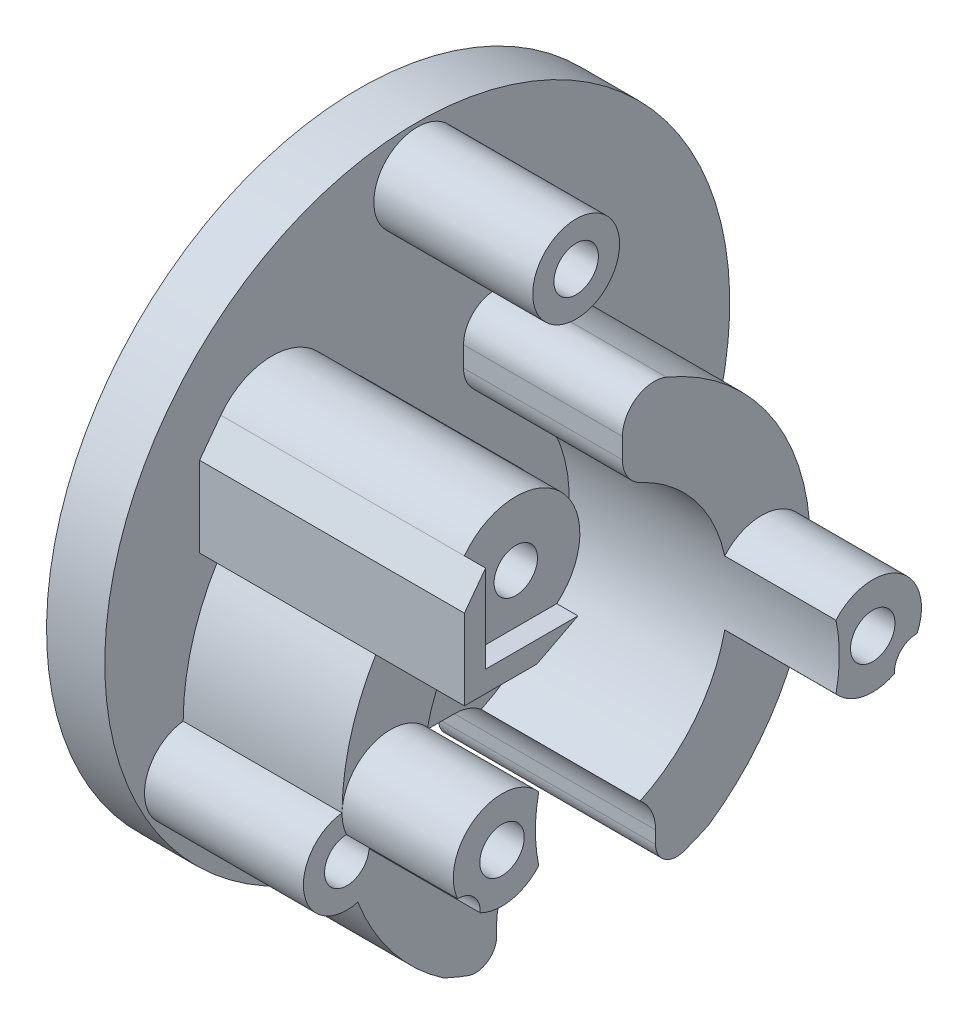
SolidWorks part; units mm, degrees
note: The reader was unsure of these and kept them because the rebuilt part matched: shared geometry of "Sketch1<3>", "Sketch1<4>", "Sketch1<5>", "Sketch3<2>", "Sketch7<4>".
material "ABS"
ref_plane "Front Plane" through (0, 0, 0) normal (0, 0, 1) x (1, 0, 0)
ref_plane "Top Plane" through (0, 0, 0) normal (0, 1, 0) x (1, 0, 0)
ref_plane "Right Plane" through (0, 0, 0) normal (1, 0, 0) x (0, 0, -1)
sketch "Sketch1" plane through (0, 0, 0) normal (1, 0, 0) x (0, 0, -1)
  line L0 (-17.5, -8.5) -> (17.5, -8.5) construction
  line L1 (-8.1298, -20.3249) -> (-12.5205, -26.7112) construction
  line L2 (8.1298, -20.3249) -> (12.5205, -26.7112) construction
  circle A0 centre (0, 0) radius 29.5
  circle A1 centre (-17.5, -8.5) radius 2.1
  circle A2 centre (17.5, -8.5) radius 2.1
  arc A3 (-14.0289, -5.4814) -> (-14.0289, -11.5186) centre (-17.5, -8.5) ccw
  arc A4 (14.0289, -11.5186) -> (14.0289, -5.4814) centre (17.5, -8.5) ccw
  arc A5 (-14.0289, -11.5186) -> (14.0289, -11.5186) centre (0, -8.5) ccw
  arc A6 (-22.1, -8.5) -> (-12.5205, -26.7112) centre (0, -8.5) ccw
  arc A7 (12.5205, -26.7112) -> (22.1, -8.5) centre (0, -8.5) ccw
  arc A8 (12.5205, -26.7112) -> (-12.5205, -26.7112) centre (0, -8.5) ccw
  circle A9 centre (0, -8.5) radius 14.35
  arc A10 (-12.5205, -26.7112) -> (-8.1298, -20.3249) centre (-10.3252, -23.518) ccw
  arc A11 (8.1298, -20.3249) -> (12.5205, -26.7112) centre (10.3252, -23.518) ccw
  circle A12 centre (17.5, -8.5) radius 4.6 construction
  circle A13 centre (-17.5, -8.5) radius 4.6 construction
  dimension "D1" = 4.2
  dimension "D2" = 4.2
  dimension "D4" = 59
  dimension "D8" = 28.7
  dimension "D3" = 35
  dimension "D5" = 17.5
  dimension "D6" = 8.5
  dimension "D7" = 2.5
extrude "Boss-Extrude1" add sketch "Sketch1" along normal blind 3 contours A0 A7 A4 A5 A3 A6 | L0 A3 A5 A4 | A9
extrude "Boss-Extrude2" add sketch "Sketch1<3>" along normal blind 28.5 contours A3 A1 | A4 A2
sketch "Sketch1<3>" plane through (0, 0, 0) normal (1, 0, 0) x (0, 0, -1) same geometry as "Sketch1"
extrude "Boss-Extrude3" add sketch "Sketch1<4>" along normal blind 18 contours A9 A5 | A9 A4 A8 A3 | A8 A7 A0 A6
sketch "Sketch1<4>" plane through (0, 0, 0) normal (1, 0, 0) x (0, 0, -1) same geometry as "Sketch1"
extrude "Boss-Extrude4" add sketch "Sketch1<5>" along normal blind 18 contours A9 A4 A8 A3
sketch "Sketch1<5>" plane through (0, 0, 0) normal (1, 0, 0) x (0, 0, -1) same geometry as "Sketch1"
sketch "Sketch3" plane through (0, 0, 0) normal (-1, 0, 0) x (0, 0, 1)
  line L0 (0, 0) -> (0, 29.5) construction
  circle A0 centre (0, 0) radius 29.5 construction
  circle A1 centre (0, 25) radius 2.1
  circle A2 centre (0, 25) radius 4.1
  circle A3 centre (21.6506, -12.5) radius 4.1
  circle A4 centre (21.6506, -12.5) radius 2.1
  circle A5 centre (-21.6506, -12.5) radius 4.1
  circle A6 centre (-21.6506, -12.5) radius 2.1
  dimension "D1" = 4.2
  dimension "D2" = 25
  dimension "D3" = 2
  dimension "D4" = 3
extrude "Boss-Extrude5" add sketch "Sketch3" against normal up to surface (18 mm away) up to face at (18, -8.5, -19.6)
extrude "Cut-Extrude1" cut sketch "Sketch3<2>" against normal through all contours A6 | L0 A1 | A1 L0 | A4
sketch "Sketch3<2>" plane through (0, 0, 0) normal (-1, 0, 0) x (0, 0, 1) same geometry as "Sketch3"
sketch "Sketch4" plane through (18, 0, 0) normal (1, 0, 0) x (0, 0, -1)
  line L0 (0, -22.75) -> (0, -29.5) construction
  line L1 (-7.5, -22.75) -> (-7.5, -29.5)
  line L2 (7.5, -22.75) -> (7.5, -29.5)
  line L7 (-7.5, -22.75) -> (-7.5, -20.6166)
  line L8 (-7.5, -20.6166) -> (7.5, -20.6166)
  line L9 (7.5, -22.75) -> (7.5, -20.6166)
  line L11 (-7.5, -29.5) -> (-7.5, -30.4306)
  line L12 (-7.5, -30.4306) -> (7.5, -30.4306)
  line L13 (7.5, -29.5) -> (7.5, -30.4306)
  dimension "D1" = 7.5
  dimension "D2" = 7.5
extrude "Cut-Extrude4" cut sketch "Sketch4" against normal through all
fillet "Fillet1" radius 4 2 edges at (1.5, -20.6166, -7.5) (1.5, -20.6166, 7.5)
fillet "Fillet2" radius 2 2 edges at (9, -28.5307, 7.5) (9, -28.5307, -7.5)
sketch "Sketch5" plane through (0, 0, 0) normal (-1, 0, 0) x (0, 0, 1)
  line L3 (7.5, -24.6166) -> (7.5, -25.807)
  line L4 (-7.5, -25.807) -> (-7.5, -24.6166)
  line L5 (-3.5, -20.6166) -> (3.5, -20.6166)
  line L6 (7.5, -24.6166) -> (7.5, -25.807)
  line L7 (-7.5, -25.807) -> (-7.5, -24.6166)
  line L8 (-3.5, -20.6166) -> (3.5, -20.6166)
  circle A0 centre (21.6506, -12.5) radius 2.1 construction
  circle A1 centre (0, 25) radius 2.1 construction
  circle A2 centre (-21.6506, -12.5) radius 2.1 construction
  circle A3 centre (21.6506, -12.5) radius 2.1
  circle A4 centre (0, 25) radius 2.1
  arc A5 (7.5, -25.807) -> (10.1909, -27.6838) centre (9.5, -25.807) ccw
  arc A6 (10.1909, -27.6838) -> (-10.1909, -27.6838) centre (0, 0) ccw
  arc A7 (-10.1909, -27.6838) -> (-7.5, -25.807) centre (-9.5, -25.807) ccw
  arc A8 (-3.5, -20.6166) -> (-7.5, -24.6166) centre (-3.5, -24.6166) ccw
  arc A9 (7.5, -24.6166) -> (3.5, -20.6166) centre (3.5, -24.6166) ccw
  arc A10 (7.5, -25.807) -> (10.1909, -27.6838) centre (9.5, -25.807) ccw
  arc A11 (10.1909, -27.6838) -> (-10.1909, -27.6838) centre (0, 0) ccw
  arc A12 (-10.1909, -27.6838) -> (-7.5, -25.807) centre (-9.5, -25.807) ccw
  arc A13 (-3.5, -20.6166) -> (-7.5, -24.6166) centre (-3.5, -24.6166) ccw
  arc A14 (7.5, -24.6166) -> (3.5, -20.6166) centre (3.5, -24.6166) ccw
  circle A15 centre (-21.6506, -12.5) radius 2.1
  dimension "D1" = 0
extrude "Boss-Extrude6" add sketch "Sketch5" along normal blind 2.5
sketch "Sketch6" plane through (3, 0, 0) normal (1, 0, 0) x (0, 0, -1)
  line L0 (-17.2374, 23.9399) -> (-1.8128, 23.9399)
  line L1 (-17.2374, 22.9399) -> (-2.1475, 22.9399)
  line L2 (-18.5475, 22.094) -> (-18.5475, 6.5399)
  line L3 (-18.5475, 6.5399) -> (-2.1475, 6.5399)
  line L4 (-2.1475, 22.9399) -> (-2.1475, 6.5399)
  line L5 (-1.1475, 23.2412) -> (-1.1475, 5.804)
  line L6 (-19.5475, 5.5399) -> (-2.9669, 5.5399)
  line L7 (-19.5475, 22.094) -> (-19.5475, 5.5399)
  line L8 (-19.5475, 23.9399) -> (-1.1475, 23.9399) construction
  line L9 (-19.5475, 23.9399) -> (-19.5475, 5.5399) construction
  line L10 (-1.1475, 23.9399) -> (-1.1475, 5.5399) construction
  line L11 (-19.5475, 5.5399) -> (-1.1475, 5.5399) construction
  line L12 (-19.5475, 22.094) -> (-18.5475, 22.094)
  line L13 (-17.2374, 23.9399) -> (-17.2374, 22.9399)
  line L14 (-18.5475, 22.9399) -> (-2.1475, 22.9399) construction
  line L15 (-18.5475, 22.9399) -> (-18.5475, 6.5399) construction
  arc A0 (14.0289, -5.4814) -> (-14.0289, -5.4814) centre (0, -8.5) ccw construction
  arc A1 (-1.1475, 5.804) -> (-2.9669, 5.5399) centre (0, -8.5) ccw
  circle A2 centre (0, 25) radius 2.1 construction
  arc A3 (-1.8128, 23.9399) -> (-1.1475, 23.2412) centre (0, 25) ccw
  dimension "D4" = 1
sketch "Sketch7" plane through (3, 0, 0) normal (1, 0, 0) x (0, 0, -1)
  line L0 (-13.7, 11.2) -> (-18.55, 11.2) construction
  line L1 (-13.7, 11.2) -> (-13.7, 6.55) construction
  line L2 (-18.55, 11.2) -> (-18.55, 6.55)
  line L3 (-18.55, 6.55) -> (-13.7, 6.55)
  line L4 (-13.7, 6.55) -> (-9.8296, 6.55)
  line L5 (-18.55, 11.2) -> (-18.55, 14.8166)
  line L6 (-20.55, 4.55) -> (-13.7, 4.55)
  line L8 (-20.55, 11.2) -> (-20.55, 12.1346)
  line L9 (-20.55, 11.2) -> (-20.55, 4.55)
  line L10 (-13.7, 4.55) -> (-9.1635, 4.55) construction
  line L11 (-13.7, 4.55) -> (-9.8296, 6.55)
  line L13 (-20.55, 11.2) -> (-20.55, 15.4285) construction
  line L14 (-18.55, 14.8166) -> (-20.55, 12.1346)
  circle A0 centre (-13.7, 11.2) radius 2.05
  arc A2 (22.0999, -8.4247) -> (-22.0999, -8.4247) centre (0, -8.5) ccw construction
  arc A3 (-9.7577, 11.3292) -> (-12.3471, 9.8292) centre (0, -8.5) ccw
  arc A4 (12.5205, -26.7112) -> (-12.5205, -26.7112) centre (0, 0) ccw construction
  arc A5 (-19.9742, 21.709) -> (-21.4742, 20.2265) centre (0, 0) ccw
  arc A6 (-9.8296, 6.55) -> (-18.55, 14.8166) centre (-13.7, 11.2) ccw
  circle A7 centre (-13.7, 11.2) radius 6.05 construction
  arc A9 (-9.1635, 4.55) -> (-20.55, 15.4285) centre (-13.7, 11.2) ccw construction
  arc M7 (-22.0999, -8.4247) -> (22.0999, -8.4247) centre (0, -8.5) cw
  dimension "D1" = 4.1
  dimension "D2" = 4.85
  dimension "D3" = 4.65
  dimension "D6" = 19.7
  dimension "D4" = 13.7
  dimension "D5" = 4
  dimension "D7" = 2
extrude "Boss-Extrude8" add sketch "Sketch7" along normal blind 23 contours A6 L5 L2 L3 A0 M7 | L4 A6 A0 L3 M7
extrude "Boss-Extrude10" add sketch "Sketch7<4>" along normal blind 25 contours L5 L14 L8 L9 L6 L3 L2 M7 | L6 L11 L4 L3 M7
sketch "Sketch7<4>" plane through (3, 0, 0) normal (1, 0, 0) x (0, 0, -1) same geometry as "Sketch7"
sketch "Sketch8" plane through (26, 0, 0) normal (1, 0, 0) x (0, 0, -1)
  circle A0 centre (-13.7, 11.2) radius 2.05 construction
  circle A1 centre (-13.7, 11.2) radius 2.05
extrude "Cut-Extrude5" cut sketch "Sketch8" against normal up to surface (23 mm away) up to face at (3, -14.1163, 0)
sketch "Sketch9" plane through (18, 0, 0) normal (1, 0, 0) x (0, 0, -1)
  line L0 (0, 13.6) -> (0, 5.85) construction
  line L2 (-4.3696, 16.5587) -> (4.3696, 16.5587)
  line L3 (-4.3696, 16.5587) -> (-4.3696, 2.8913)
  line L4 (-4.3696, 2.8913) -> (4.3696, 2.8913)
  line L5 (4.3696, 16.5587) -> (4.3696, 2.8913)
  line L6 (-4.3696, 16.5587) -> (4.3696, 2.8913) construction
  line L7 (-4.3696, 2.8913) -> (4.3696, 16.5587) construction
  arc A1 (22.0999, -8.4247) -> (-7.7337, 12.2027) centre (0, -8.5) ccw construction
  point P0 (0, 9.725)
extrude "Cut-Extrude6" cut sketch "Sketch9" against normal up to surface (15 mm away) up to face at (3, -14.1163, 0)
fillet "Fillet6" radius 3 4 edges at (10.5, 5.1685, 4.3696) (10.5, 5.1685, -4.3696) (10.5, 13.1637, -4.3696) (10.5, 13.1637, 4.3696)
